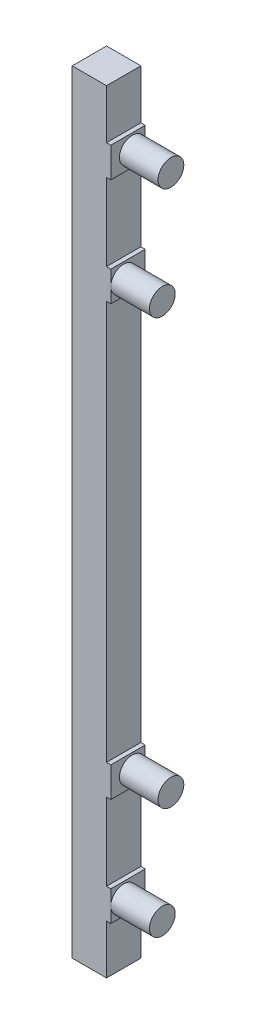
SolidWorks part; units mm, degrees
material "6061 Alloy"
ref_plane "Спереди" through (0, 0, 0) normal (0, 0, 1) x (1, 0, 0)
ref_plane "Сверху" through (0, 0, 0) normal (0, 1, 0) x (1, 0, 0)
ref_plane "Справа" through (0, 0, 0) normal (1, 0, 0) x (0, 0, -1)
other "Configuration Table"
sketch "Sketch1" plane through (0, 0, 0) normal (1, 0, 0) x (0, 0, -1)
  line L1 (-4, -90) -> (4, -90)
  line L2 (-4, -90) -> (-4, 90)
  line L3 (-4, 90) -> (4, 90)
  line L4 (4, -90) -> (4, 90)
  line L5 (-4, -90) -> (4, 90) construction
  line L6 (-4, 90) -> (4, -90) construction
  point P0 (0, 0)
  point P14 (0, 0)
  point P15 (0, 0)
  dimension "D1" = 8
  dimension "D2" = 180
extrude "Boss-Extrude1" add sketch "Sketch1" along normal blind 8 contours L4 L3 L2 L1 region at (0, 0, 0)
sketch "Sketch3" plane through (8, 0, 0) normal (1, 0, 0) x (0, 0, -1)
  line L0 (4, -90) -> (4, 90) construction
  line L1 (-4, -90) -> (-4, 90) construction
  line L2 (-64.321, -1.4938) -> (-64.0869, 0) construction
  line L3 (-64.0869, 0) -> (66.0456, 0) construction
  line L4 (-4, 78.5) -> (4, 78.5)
  line L5 (4, 78.5) -> (4, 71.5)
  line L6 (4, 71.5) -> (-4, 71.5)
  line L7 (-4, 71.5) -> (-4, 78.5)
  line L8 (5.3983, 75) -> (-6.1844, 75) construction
  line L9 (-4, 53.5) -> (4, 53.5)
  line L10 (4, 53.5) -> (4, 46.5)
  line L11 (4, 46.5) -> (-4, 46.5)
  line L12 (-4, 46.5) -> (-4, 53.5)
  line L13 (-4.571, 50) -> (4.5329, 50) construction
  line L14 (-4, -46.5) -> (4, -46.5)
  line L15 (4, -46.5) -> (4, -53.5)
  line L16 (4, -53.5) -> (-4, -53.5)
  line L17 (-4, -53.5) -> (-4, -46.5)
  line L18 (-4, -71.5) -> (4, -71.5)
  line L19 (4, -71.5) -> (4, -78.5)
  line L20 (4, -78.5) -> (-4, -78.5)
  line L21 (-4, -78.5) -> (-4, -71.5)
  line L22 (-5.1493, -50) -> (6.5513, -50) construction
  line L23 (-4.8834, -75) -> (5.6206, -75) construction
  circle A0 centre (1, 75) radius 3
  circle A1 centre (-1, 50) radius 3
  circle A2 centre (1, -50) radius 3
  circle A3 centre (-1, -75) radius 3
  line M27 (4, -90) -> (4, 90)
  line M29 (-4, 90) -> (-4, -90)
  dimension "D1" = 6
  dimension "D2" = 25
  dimension "D3" = 25
  dimension "D4" = 50
  dimension "D5" = 50
  dimension "D6" = 7
  dimension "D7" = 7
  dimension "D8" = 7
  dimension "D9" = 7
extrude "Boss-Extrude4" add sketch "Sketch3" along normal blind 10 contours A3 | A2 | A1 | A0 region at (8, 50, 1) region at (8, -50, -1) region at (8, -75, 1)
extrude "Boss-Extrude5" add sketch "Sketch3<4>" along normal blind 1 contours A0 L5 L4 L6 M27 M29 | A0 | A1 L12 L11 L9 M29 M27 | A1 | A2 L15 L14 L16 M27 M29 | A2 | A3 | L21 L18 L19 L20 region at (8, 75, -1) region at (8, 78.3937, 0) region at (8, 50, 1) region at (8, 53.3937, 0) region at (8, -50, -1) region at (8, -48.25, -3.8937) region at (8, -75, 1)
sketch "Sketch3<4>" plane through (8, 0, 0) normal (1, 0, 0) x (0, 0, -1) same geometry as "Sketch3"
equation "\"D3@Sketch3\"=\"D2@Sketch3\""
equation "\"D5@Sketch3\"=\"D4@Sketch3\""
equation "\"D7@Sketch3\"=\"D6@Sketch3\""
